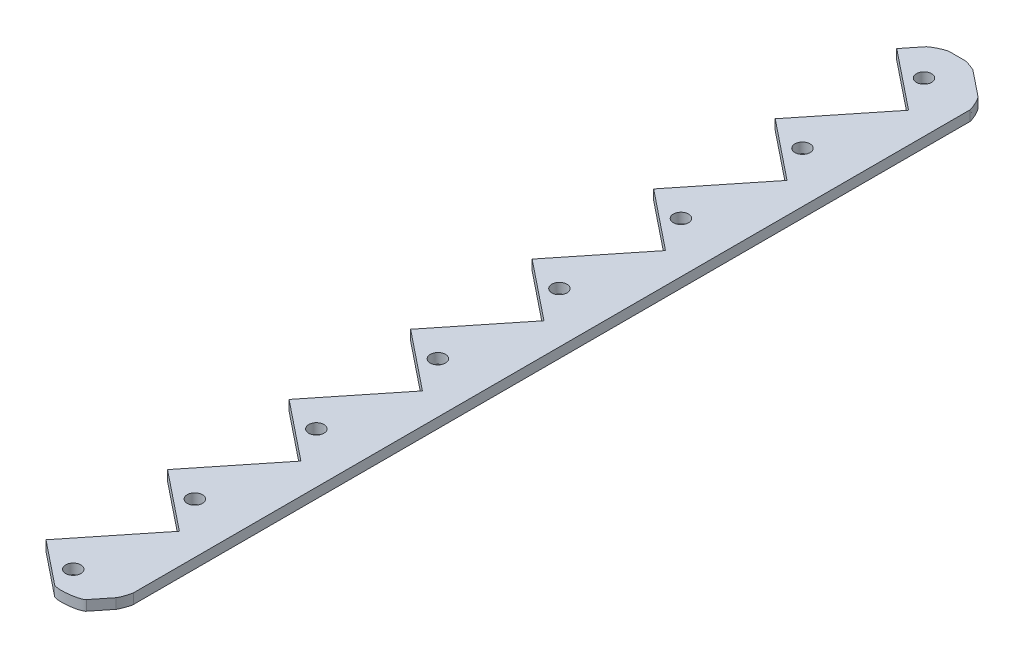
SolidWorks part; units mm, degrees
ref_plane "Front Plane" through (0, 0, 0) normal (0, 0, 1) x (1, 0, 0)
ref_plane "Top Plane" through (0, 0, 0) normal (0, 1, 0) x (1, 0, 0)
ref_plane "Right Plane" through (0, 0, 0) normal (1, 0, 0) x (0, 0, -1)
sketch "Sketch1" plane through (0, 0, 0) normal (0, 1, 0) x (1, 0, 0)
  line L0 (-13.635, -43.1454) -> (0.2556, -60.4948) construction
  line L5 (-13.635, -43.1454) -> (-22.9293, -50.5868) construction
  line L6 (-22.9293, -50.5868) -> (-9.0387, -67.9362) construction
  line L7 (-22.1678, 36.7724) -> (28.6322, 36.7724) construction
  line L8 (-22.1678, 36.7724) -> (-22.1678, -191.8276) construction
  line L9 (-22.1678, -191.8276) -> (28.6322, -191.8276) construction
  line L10 (28.6322, 36.7724) -> (28.6322, -191.8276) construction
  line L11 (0.2556, -60.4948) -> (-9.0387, -67.9362) construction
  line L12 (-13.635, -24.0954) -> (0.2556, -41.4448) construction
  line L13 (-13.635, -24.0954) -> (-22.9293, -31.5368) construction
  line L14 (-22.9293, -31.5368) -> (-9.0387, -48.8862) construction
  line L15 (-8.1122, -59.5683) -> (-27.1622, -59.5683) construction
  line L16 (-8.1122, -59.5683) -> (-8.1122, -40.5183) construction
  line L17 (0.2556, -41.4448) -> (-9.0387, -48.8862) construction
  line L18 (-8.1122, -40.5183) -> (-27.1622, -40.5183) construction
  line L19 (-8.1122, -40.5183) -> (-8.1122, -21.4683) construction
  line L20 (-13.635, -100.2954) -> (0.2556, -117.6448) construction
  line L21 (-13.635, -100.2954) -> (-22.9293, -107.7368) construction
  line L22 (-22.9293, -107.7368) -> (-9.0387, -125.0862) construction
  line L23 (0.2556, -117.6448) -> (-9.0387, -125.0862) construction
  line L24 (-13.635, -81.2454) -> (0.2556, -98.5948) construction
  line L25 (-13.635, -81.2454) -> (-22.9293, -88.6868) construction
  line L26 (-22.9293, -88.6868) -> (-9.0387, -106.0362) construction
  line L27 (-8.1122, -116.7183) -> (-27.1622, -116.7183) construction
  line L28 (-8.1122, -116.7183) -> (-8.1122, -97.6683) construction
  line L29 (0.2556, -98.5948) -> (-9.0387, -106.0362) construction
  line L30 (-8.1122, -97.6683) -> (-27.1622, -97.6683) construction
  line L31 (-8.1122, -97.6683) -> (-8.1122, -78.6183) construction
  line L32 (-13.635, -5.0454) -> (0.2556, -22.3948) construction
  line L33 (-13.635, -5.0454) -> (-22.9293, -12.4868) construction
  line L34 (-13.635, 14.0046) -> (0.2556, -3.3448) construction
  line L35 (-13.635, 14.0046) -> (-22.9293, 6.5632) construction
  line L36 (-22.9293, 6.5632) -> (-9.0387, -10.7862) construction
  line L37 (0.2556, -3.3448) -> (-9.0387, -10.7862) construction
  line L38 (-22.9293, -12.4868) -> (-9.0387, -29.8362) construction
  line L39 (0.2556, -22.3948) -> (-9.0387, -29.8362) construction
  line L40 (-13.635, 33.0546) -> (0.2556, 15.7052) construction
  line L41 (-13.635, 33.0546) -> (-22.9293, 25.6132) construction
  line L42 (-22.9293, 25.6132) -> (-9.0387, 8.2638) construction
  line L43 (0.2556, 15.7052) -> (-9.0387, 8.2638) construction
  line L44 (-8.1122, -21.4683) -> (-27.1622, -21.4683) construction
  line L45 (-8.1122, -21.4683) -> (-8.1122, -2.4183) construction
  line L46 (-13.635, -62.1954) -> (0.2556, -79.5448) construction
  line L47 (-13.635, -62.1954) -> (-22.9293, -69.6368) construction
  line L48 (-22.9293, -69.6368) -> (-9.0387, -86.9862) construction
  line L49 (0.2556, -79.5448) -> (-9.0387, -86.9862) construction
  line L50 (-8.1122, -78.6183) -> (-27.1622, -78.6183) construction
  line L51 (-8.1122, -78.6183) -> (-8.1122, -59.5683) construction
  line L52 (-8.1122, -2.4183) -> (-27.1622, -2.4183) construction
  line L53 (-8.1122, -2.4183) -> (-8.1122, 16.6317) construction
  line L54 (-8.1122, 16.6317) -> (-27.1622, 16.6317) construction
  line L55 (-8.1122, 16.6317) -> (-8.1122, 35.6817) construction
  line L56 (-22.9293, 25.6132) -> (-25.9059, 29.3309) construction
  line L57 (-25.9059, 29.3309) -> (-16.6116, 36.7724) construction
  line L58 (-16.6116, 36.7724) -> (-13.635, 33.0546) construction
  line L59 (-24.4176, 27.4721) -> (-15.1233, 34.9135) construction
  line L60 (-25.9059, 28.8165) -> (-25.9059, 40.1202) construction
  line L61 (-9.0387, 8.2638) -> (-6.0621, 4.5461) construction
  line L62 (-8.1122, 36.5878) -> (-8.1122, -24.5097) construction
  line L63 (-6.0621, 4.5461) -> (3.2322, 11.9875) construction
  line L64 (0.2556, 15.7052) -> (3.2322, 11.9875) construction
  line L65 (1.7439, 13.8464) -> (-7.5504, 6.405) construction
  line L66 (-19.7704, 30.6783) -> (-19.7704, 38.979) construction
  line L67 (-2.9032, 9.6112) -> (-2.9032, 17.9119) construction
  line L68 (3.2322, 11.4731) -> (3.2322, 48.1829) construction
  line L69 (4.7205, 13.8464) -> (14.0148, 6.405) construction
  line L70 (6.2088, 15.7052) -> (3.2322, 11.9875) construction
  line L71 (12.5265, 4.5461) -> (3.2322, 11.9875) construction
  line L72 (15.5031, 8.2638) -> (12.5265, 4.5461) construction
  line L73 (30.882, 27.4721) -> (21.5877, 34.9135) construction
  line L74 (23.0759, 36.7724) -> (20.0994, 33.0546) construction
  line L75 (32.3703, 29.3309) -> (23.0759, 36.7724) construction
  line L76 (29.3937, 25.6132) -> (32.3703, 29.3309) construction
  line L77 (14.5766, 16.6317) -> (14.5766, 35.6817) construction
  line L78 (14.5766, 16.6317) -> (33.6266, 16.6317) construction
  line L79 (14.5766, -2.4183) -> (14.5766, 16.6317) construction
  line L80 (14.5766, -2.4183) -> (33.6266, -2.4183) construction
  line L81 (14.5766, -78.6183) -> (14.5766, -59.5683) construction
  line L82 (14.5766, -78.6183) -> (33.6266, -78.6183) construction
  line L83 (6.2088, -79.5448) -> (15.5031, -86.9862) construction
  line L84 (29.3937, -69.6368) -> (15.5031, -86.9862) construction
  line L85 (20.0994, -62.1954) -> (29.3937, -69.6368) construction
  line L86 (20.0994, -62.1954) -> (6.2088, -79.5448) construction
  line L87 (14.5766, -21.4683) -> (14.5766, -2.4183) construction
  line L88 (14.5766, -21.4683) -> (33.6266, -21.4683) construction
  line L89 (6.2088, 15.7052) -> (15.5031, 8.2638) construction
  line L90 (29.3937, 25.6132) -> (15.5031, 8.2638) construction
  line L91 (20.0994, 33.0546) -> (29.3937, 25.6132) construction
  line L92 (20.0994, 33.0546) -> (6.2088, 15.7052) construction
  line L93 (6.2088, -22.3948) -> (15.5031, -29.8362) construction
  line L94 (29.3937, -12.4868) -> (15.5031, -29.8362) construction
  line L95 (6.2088, -3.3448) -> (15.5031, -10.7862) construction
  line L96 (29.3937, 6.5632) -> (15.5031, -10.7862) construction
  line L97 (20.0994, 14.0046) -> (29.3937, 6.5632) construction
  line L98 (20.0994, 14.0046) -> (6.2088, -3.3448) construction
  line L99 (20.0994, -5.0454) -> (29.3937, -12.4868) construction
  line L100 (20.0994, -5.0454) -> (6.2088, -22.3948) construction
  line L101 (14.5766, -97.6683) -> (14.5766, -78.6183) construction
  line L102 (14.5766, -97.6683) -> (33.6266, -97.6683) construction
  line L103 (6.2088, -98.5948) -> (15.5031, -106.0362) construction
  line L104 (14.5766, -116.7183) -> (14.5766, -97.6683) construction
  line L105 (14.5766, -116.7183) -> (33.6266, -116.7183) construction
  line L106 (29.3937, -88.6868) -> (15.5031, -106.0362) construction
  line L107 (20.0994, -81.2454) -> (29.3937, -88.6868) construction
  line L108 (20.0994, -81.2454) -> (6.2088, -98.5948) construction
  line L109 (6.2088, -117.6448) -> (15.5031, -125.0862) construction
  line L110 (29.3937, -107.7368) -> (15.5031, -125.0862) construction
  line L111 (20.0994, -100.2954) -> (29.3937, -107.7368) construction
  line L112 (20.0994, -100.2954) -> (6.2088, -117.6448) construction
  line L113 (14.5766, -40.5183) -> (14.5766, -21.4683) construction
  line L114 (14.5766, -40.5183) -> (33.6266, -40.5183) construction
  line L115 (6.2088, -41.4448) -> (15.5031, -48.8862) construction
  line L116 (14.5766, -59.5683) -> (14.5766, -40.5183) construction
  line L117 (14.5766, -59.5683) -> (33.6266, -59.5683) construction
  line L118 (29.3937, -31.5368) -> (15.5031, -48.8862) construction
  line L119 (20.0994, -24.0954) -> (29.3937, -31.5368) construction
  line L120 (20.0994, -24.0954) -> (6.2088, -41.4448) construction
  line L121 (6.2088, -60.4948) -> (15.5031, -67.9362) construction
  line L122 (29.3937, -50.5868) -> (15.5031, -67.9362) construction
  line L123 (20.0994, -43.1454) -> (29.3937, -50.5868) construction
  line L124 (20.0994, -43.1454) -> (6.2088, -60.4948) construction
  line L125 (23.0759, 36.7724) -> (-16.6116, 36.7724) construction
  circle A2 centre (-8.1122, -59.5683) radius 5.9531 construction
  circle A3 centre (-8.1122, -59.5683) radius 19.05 construction
  circle A4 centre (-8.1122, -40.5183) radius 5.9531 construction
  circle A5 centre (-8.1122, -40.5183) radius 19.05 construction
  circle A6 centre (-8.1122, -116.7183) radius 5.9531 construction
  circle A7 centre (-8.1122, -116.7183) radius 19.05 construction
  circle A8 centre (-8.1122, -97.6683) radius 5.9531 construction
  circle A9 centre (-8.1122, -97.6683) radius 19.05 construction
  circle A10 centre (-8.1122, -2.4183) radius 5.9531 construction
  circle A11 centre (-8.1122, -2.4183) radius 19.05 construction
  circle A12 centre (-8.1122, 16.6317) radius 5.9531 construction
  circle A13 centre (-8.1122, 16.6317) radius 19.05 construction
  circle A14 centre (-8.1122, -21.4683) radius 5.9531 construction
  circle A15 centre (-8.1122, -21.4683) radius 19.05 construction
  circle A16 centre (-8.1122, -78.6183) radius 5.9531 construction
  circle A17 centre (-8.1122, -78.6183) radius 19.05 construction
  circle A18 centre (-19.7704, 31.1928) radius 1.1906
  circle A19 centre (-2.9032, 10.1257) radius 1.1906
  circle A20 centre (14.5766, -78.6183) radius 19.05 construction
  circle A21 centre (14.5766, -78.6183) radius 5.9531 construction
  circle A22 centre (14.5766, -21.4683) radius 19.05 construction
  circle A23 centre (14.5766, -21.4683) radius 5.9531 construction
  circle A24 centre (14.5766, 16.6317) radius 19.05 construction
  circle A25 centre (14.5766, 16.6317) radius 5.9531 construction
  circle A26 centre (14.5766, -2.4183) radius 19.05 construction
  circle A27 centre (14.5766, -2.4183) radius 5.9531 construction
  circle A28 centre (14.5766, -97.6683) radius 19.05 construction
  circle A29 centre (14.5766, -97.6683) radius 5.9531 construction
  circle A30 centre (14.5766, -116.7183) radius 19.05 construction
  circle A31 centre (14.5766, -116.7183) radius 5.9531 construction
  circle A32 centre (14.5766, -40.5183) radius 19.05 construction
  circle A33 centre (14.5766, -40.5183) radius 5.9531 construction
  circle A34 centre (14.5766, -59.5683) radius 19.05 construction
  circle A35 centre (14.5766, -59.5683) radius 5.9531 construction
  circle A36 centre (9.3676, 10.1257) radius 1.1906
  circle A37 centre (26.2348, 31.1928) radius 1.1906
  point P81 (-15.1233, 34.9135)
  point P97 (3.2322, 36.7724)
  dimension "D3" = 2.3813
  dimension "D23" = 38.1
  dimension "D1" = 4.7625
  dimension "D4" = 50.8
  dimension "D5" = 228.6
  dimension "D21" = 22.225
  dimension "D22" = 11.9062
sketch "Sketch2" plane through (0, 0, 0) normal (0, 1, 0) x (1, 0, 0)
  line L0 (-16.6116, 36.7724) -> (-13.635, 33.0546)
  line L1 (-13.635, 33.0546) -> (-22.9293, 25.6132)
  line L2 (-22.9293, 25.6132) -> (-13.635, 14.0046)
  line L3 (-18.2822, 10.2839) -> (-19.7704, 12.1428)
  line L4 (-13.635, 14.0046) -> (-22.9293, 6.5632) construction
  line L5 (-19.7704, -199969.3217) -> (-19.7704, 200038.979) construction
  line L6 (3.2322, 37.6418) -> (3.2322, 34.7632) construction
  line L7 (-9.0387, -10.7862) -> (0.2556, -22.3948)
  line L8 (3.2322, -199988.5269) -> (3.2322, 200048.1829) construction
  line L9 (-13.635, 14.0046) -> (-22.9293, 6.5632)
  line L10 (-22.9293, 6.5632) -> (-13.635, -5.0454)
  line L11 (-13.635, -5.0454) -> (-22.9293, -12.4868)
  line L12 (-22.9293, -12.4868) -> (-13.635, -24.0954)
  line L13 (-13.635, -24.0954) -> (-22.9293, -31.5368)
  line L14 (-22.9293, -31.5368) -> (-13.635, -43.1454)
  line L15 (-13.635, -43.1454) -> (-22.9293, -50.5868)
  line L16 (-22.9293, -50.5868) -> (-13.635, -62.1954)
  line L17 (-13.635, -62.1954) -> (-22.9293, -69.6368)
  line L18 (-22.9293, -69.6368) -> (-13.635, -81.2454)
  line L19 (-13.635, -81.2454) -> (-22.9293, -88.6868)
  line L20 (-22.9293, -88.6868) -> (-13.635, -100.2954)
  line L21 (-13.635, -100.2954) -> (-22.9293, -107.7368)
  line L22 (-22.9293, -107.7368) -> (-13.635, -119.3454)
  line L23 (0.2556, 15.7052) -> (-9.0387, 8.2638)
  line L24 (-9.0387, 8.2638) -> (0.2556, -3.3448)
  line L25 (0.2556, -3.3448) -> (-9.0387, -10.7862)
  line L26 (-9.0387, -29.8362) -> (0.2556, -41.4448)
  line L27 (0.2556, -22.3948) -> (-9.0387, -29.8362)
  line L28 (-9.0387, -48.8862) -> (0.2556, -60.4948)
  line L29 (0.2556, -41.4448) -> (-9.0387, -48.8862)
  line L30 (-9.0387, -67.9362) -> (0.2556, -79.5448)
  line L31 (0.2556, -60.4948) -> (-9.0387, -67.9362)
  line L32 (-9.0387, -86.9862) -> (0.2556, -98.5948)
  line L33 (0.2556, -79.5448) -> (-9.0387, -86.9862)
  line L34 (-9.0387, -106.0362) -> (0.2556, -117.6448)
  line L35 (0.2556, -98.5948) -> (-9.0387, -106.0362)
  line L37 (0.2556, -117.6448) -> (-9.0387, -125.0862)
  line L38 (6.2088, -117.6448) -> (15.5031, -125.0862)
  line L39 (-9.0387, -125.0862) -> (0.2556, -136.6948) [skipped]
  line L41 (-22.9293, 25.6132) -> (-27.6918, 25.6132) construction
  line L42 (-16.6116, 36.7724) -> (-27.6918, 36.7724)
  line L43 (-27.6918, 36.7724) -> (-27.6918, -124.1079)
  line L44 (-13.635, -119.3454) -> (-13.635, -124.1079)
  line L45 (-13.635, -124.1079) -> (-27.6918, -124.1079)
  line L47 (6.2088, -98.5948) -> (15.5031, -106.0362)
  line L48 (15.5031, -106.0362) -> (6.2088, -117.6448)
  line L49 (6.2088, -79.5448) -> (15.5031, -86.9862)
  line L50 (15.5031, -86.9862) -> (6.2088, -98.5948)
  line L51 (6.2088, -60.4948) -> (15.5031, -67.9362)
  line L52 (15.5031, -67.9362) -> (6.2088, -79.5448)
  line L53 (6.2088, -41.4448) -> (15.5031, -48.8862)
  line L54 (15.5031, -48.8862) -> (6.2088, -60.4948)
  line L55 (6.2088, -22.3948) -> (15.5031, -29.8362)
  line L56 (15.5031, -29.8362) -> (6.2088, -41.4448)
  line L57 (6.2088, -3.3448) -> (15.5031, -10.7862)
  line L58 (15.5031, 8.2638) -> (6.2088, -3.3448)
  line L59 (6.2088, 15.7052) -> (15.5031, 8.2638)
  line L60 (15.5031, -10.7862) -> (6.2088, -22.3948)
  line L61 (0.2556, 15.7052) -> (6.2088, 15.7052)
  line L62 (29.3937, 25.6132) -> (34.1562, 25.6132) construction
  line L63 (20.0994, -124.1079) -> (34.1562, -124.1079)
  line L64 (20.0994, -119.3454) -> (20.0994, -124.1079)
  line L65 (34.1562, 36.7724) -> (34.1562, -124.1079)
  line L66 (23.0759, 36.7724) -> (34.1562, 36.7724)
  line L67 (29.3937, -107.7368) -> (20.0994, -119.3454)
  line L68 (20.0994, -100.2954) -> (29.3937, -107.7368)
  line L69 (29.3937, -88.6868) -> (20.0994, -100.2954)
  line L70 (20.0994, -81.2454) -> (29.3937, -88.6868)
  line L71 (29.3937, -69.6368) -> (20.0994, -81.2454)
  line L72 (20.0994, -62.1954) -> (29.3937, -69.6368)
  line L73 (29.3937, -50.5868) -> (20.0994, -62.1954)
  line L74 (20.0994, -43.1454) -> (29.3937, -50.5868)
  line L75 (29.3937, -31.5368) -> (20.0994, -43.1454)
  line L76 (20.0994, -24.0954) -> (29.3937, -31.5368)
  line L77 (29.3937, -12.4868) -> (20.0994, -24.0954)
  line L78 (20.0994, -5.0454) -> (29.3937, -12.4868)
  line L79 (29.3937, 6.5632) -> (20.0994, -5.0454)
  line L80 (20.0994, 14.0046) -> (29.3937, 6.5632)
  line L81 (24.7465, 10.2839) -> (26.2348, 12.1428)
  line L82 (29.3937, 25.6132) -> (20.0994, 14.0046)
  line L83 (20.0994, 33.0546) -> (29.3937, 25.6132)
  line L84 (23.0759, 36.7724) -> (20.0994, 33.0546)
  line L85 (-27.6918, 31.9683) -> (-21.6916, 36.7724)
  line L86 (28.1559, 36.7724) -> (34.1562, 31.9683)
  line L87 (-22.9293, -107.7368) -> (-27.6918, -101.7884)
  line L88 (29.3937, -107.7368) -> (34.1562, -101.7884)
  line L89 (-9.0387, -125.0862) -> (-6.0621, -128.8039)
  line L90 (15.5031, -125.0862) -> (12.5265, -128.8039)
  line L91 (-6.0621, -128.8039) -> (12.5265, -128.8039)
  line L92 (-25.9059, 29.3309) -> (-16.6116, 36.7724) construction
  line L93 (32.3703, 29.3309) -> (23.0759, 36.7724) construction
  circle A0 centre (-19.7704, 31.1928) radius 1.1906
  circle A1 centre (-19.7704, 31.1928) radius 1.1906 construction
  circle A2 centre (-19.7704, 12.1428) radius 1.1906
  circle A3 centre (-19.7704, -6.9072) radius 1.1906
  circle A4 centre (-19.7704, -25.9572) radius 1.1906
  circle A5 centre (-19.7704, -45.0072) radius 1.1906
  circle A6 centre (-19.7704, -64.0572) radius 1.1906
  circle A7 centre (-19.7704, -83.1072) radius 1.1906
  circle A8 centre (-19.7704, -102.1572) radius 1.1906
  circle A9 centre (-2.9032, 10.1257) radius 1.1906
  circle A10 centre (-2.9032, 10.1257) radius 1.1906 construction
  circle A11 centre (-2.9032, -8.9243) radius 1.1906
  circle A12 centre (-2.9032, -27.9743) radius 1.1906
  circle A13 centre (-2.9032, -47.0243) radius 1.1906
  circle A14 centre (-2.9032, -66.0743) radius 1.1906
  circle A15 centre (-2.9032, -85.1243) radius 1.1906
  circle A16 centre (-2.9032, -104.1743) radius 1.1906
  circle A17 centre (-2.9032, -123.2243) radius 1.1906
  circle A18 centre (9.3676, -123.2243) radius 1.1906
  circle A19 centre (9.3676, -104.1743) radius 1.1906
  circle A20 centre (9.3676, -85.1243) radius 1.1906
  circle A21 centre (9.3676, -66.0743) radius 1.1906
  circle A22 centre (9.3676, -47.0243) radius 1.1906
  circle A23 centre (9.3676, -27.9743) radius 1.1906
  circle A24 centre (9.3676, -8.9243) radius 1.1906
  circle A25 centre (9.3676, 10.1257) radius 1.1906
  circle A26 centre (26.2348, -102.1572) radius 1.1906
  circle A27 centre (26.2348, -83.1072) radius 1.1906
  circle A28 centre (26.2348, -64.0572) radius 1.1906
  circle A29 centre (26.2348, -45.0072) radius 1.1906
  circle A30 centre (26.2348, -25.9572) radius 1.1906
  circle A31 centre (26.2348, -6.9072) radius 1.1906
  circle A32 centre (26.2348, 12.1428) radius 1.1906
  circle A33 centre (26.2348, 31.1928) radius 1.1906
  dimension "D1" = 19.05
  dimension "D3" = 8
  dimension "D2" = 8
  dimension "D4" = 3.175
  dimension "D5" = 3.175
extrude "Boss-Extrude1" add sketch "Sketch2" along normal blind 1.5875 contours A32 L80 L79 L78 L77 L76 L75 L74 L73 L72 L71 L70 L69 L68 L88 L65 L86 L66 L84 L83 L82 A31 A29 A27 A26 A28 A30 A33 region at (29.0303, 0, 35.1664)
fillet "Fillet1" radius 3.175 5 edges at (29.3937, 0.7937, 107.7368) (34.1562, 0.7937, 101.7884) (34.1562, 0.7937, -31.9683) (28.1559, 0.7937, -36.7724) (23.0759, 0.7937, -36.7724) conic radius 10
